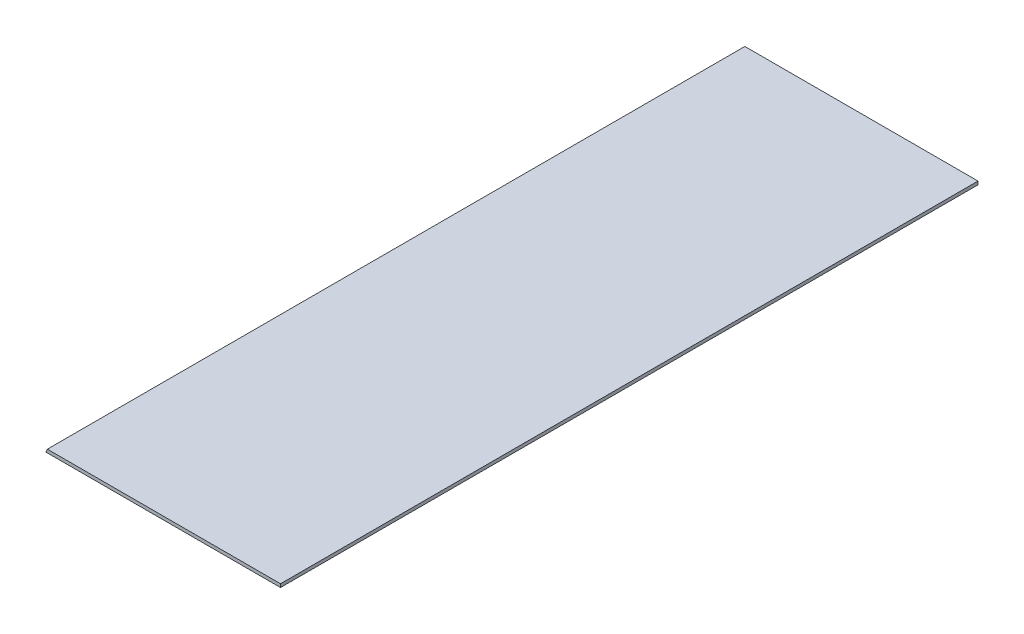
SolidWorks part; units mm, degrees
ref_plane "Front Plane" through (0, 0, 0) normal (0, 0, 1) x (1, 0, 0)
ref_plane "Top Plane" through (0, 0, 0) normal (0, 1, 0) x (1, 0, 0)
ref_plane "Right Plane" through (0, 0, 0) normal (1, 0, 0) x (0, 0, -1)
sketch "Sketch1" plane through (0, 0, 0) normal (0, 0, 1) x (1, 0, 0)
  line L0 (0, 0) -> (0.9785, 2.3622)
  line L1 (0.9785, 2.3622) -> (168.656, 2.3622)
  line L2 (168.656, 2.3622) -> (168.656, 0)
  line L3 (168.656, 0) -> (0, 0)
  dimension "D1" = 67.5
  dimension "D2" = 2.3622
  dimension "D3" = 168.656
extrude "Boss-Extrude1" add sketch "Sketch1" along normal blind 501.65
